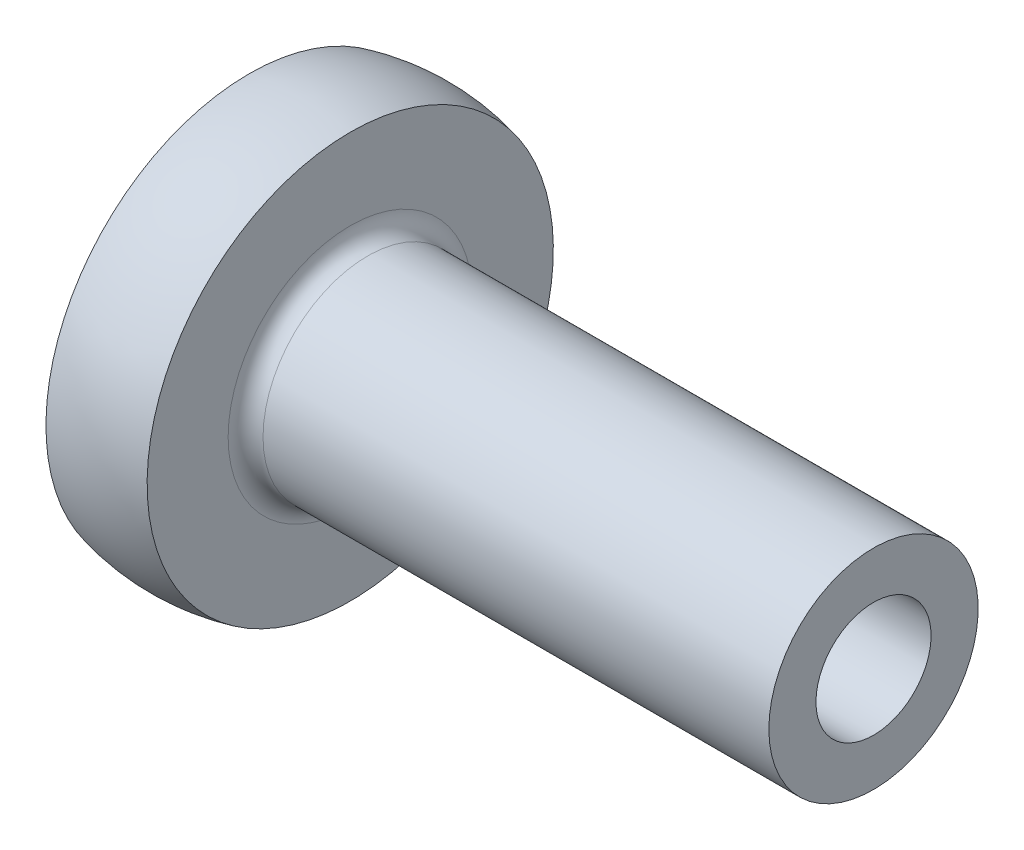
SolidWorks part; units mm, degrees
ref_plane "Front" through (0, 0, 0) normal (0, 0, 1) x (1, 0, 0)
ref_plane "Top" through (0, 0, 0) normal (0, 1, 0) x (1, 0, 0)
ref_plane "Right" through (0, 0, 0) normal (1, 0, 0) x (0, 0, -1)
sketch "Sketch1" plane through (0, 0, 0) normal (0, 0, 1) x (1, 0, 0)
  line L0 (0, 1.1644) -> (0, 0)
  line L1 (0.58, 1.1644) -> (0.58, 0.6)
  line L2 (0, 0) -> (1.9495, 0)
  line L3 (3.58, 0.33) -> (3.58, 0.6)
  line L4 (3.58, 0.6) -> (0.58, 0.6)
  line L5 (-2.3183, 0) -> (6.9456, 0) construction
  line L6 (3.58, 0.33) -> (2.14, 0.33)
  line L7 (2.14, 0.33) -> (1.9495, 0)
  arc A0 (0.58, 1.1644) -> (0, 1.1644) centre (0.29, 0) ccw
  dimension "D3" = 0.29
  dimension "D2" = 60
revolve "Base-Revolve" add sketch "Sketch1" angle 360 about L5
fillet "Fillet1" radius 0.1 1 edges at (0.58, 0, 0.6)
equation "\"D3@Sketch1\" = \"K@Sketch1\" / 2"
